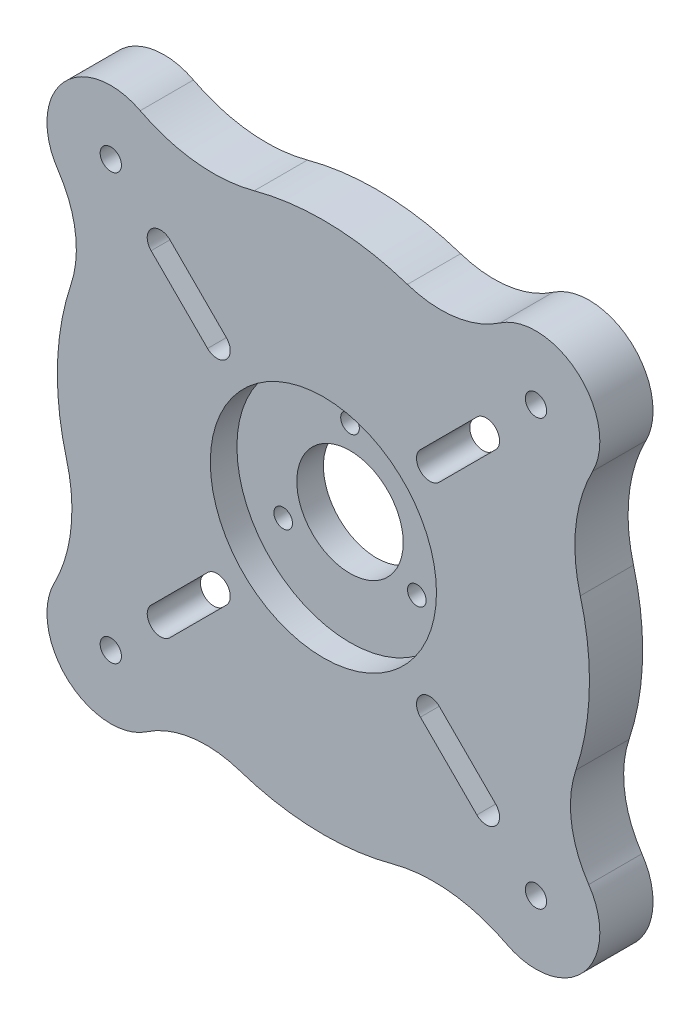
SolidWorks part; units mm, degrees
material "AISI 1020"
ref_plane "Front Plane" through (0, 0, 0) normal (0, 0, 1) x (1, 0, 0)
ref_plane "Top Plane" through (0, 0, 0) normal (0, 1, 0) x (1, 0, 0)
ref_plane "Right Plane" through (0, 0, 0) normal (1, 0, 0) x (0, 0, -1)
sketch "Sketch2" plane through (0, 0, 0) normal (0, 0, 1) x (1, 0, 0)
  line L0 (39.9515, 39.9515) -> (-39.9515, -39.9515) construction
  line L1 (48.4368, 31.4663) -> (-31.4663, -48.4368) construction
  line L2 (31.4663, 48.4368) -> (-48.4368, -31.4663) construction
  line L3 (0, 0) -> (0, 50) construction
  line L4 (-39.9515, 39.9515) -> (39.9515, -39.9515) construction
  line L5 (-48.4368, 31.4663) -> (31.4663, -48.4368) construction
  line L6 (-31.4663, 48.4368) -> (48.4368, -31.4663) construction
  line L7 (30.6066, 30.6066) -> (20, 20) construction
  line L8 (32.3744, 28.8388) -> (21.7678, 18.2322)
  line L9 (28.8388, 32.3744) -> (18.2322, 21.7678)
  line L10 (30.6066, -30.6066) -> (20, -20) construction
  line L11 (28.8388, -32.3744) -> (18.2322, -21.7678)
  line L12 (32.3744, -28.8388) -> (21.7678, -18.2322)
  line L13 (-30.6066, -30.6066) -> (-20, -20) construction
  line L14 (-32.3744, -28.8388) -> (-21.7678, -18.2322)
  line L15 (-28.8388, -32.3744) -> (-18.2322, -21.7678)
  line L16 (-30.6066, 30.6066) -> (-20, 20) construction
  line L17 (-28.8388, 32.3744) -> (-18.2322, 21.7678)
  line L18 (-32.3744, 28.8388) -> (-21.7678, 18.2322)
  circle A0 centre (0, 0) radius 50
  arc A1 (48.4368, 31.4663) -> (31.4663, 48.4368) centre (39.9515, 39.9515) ccw construction
  arc A2 (-48.4368, -31.4663) -> (-31.4663, -48.4368) centre (-39.9515, -39.9515) ccw construction
  arc A3 (-48.4368, 31.4663) -> (-31.4663, 48.4368) centre (-39.9515, 39.9515) cw construction
  arc A4 (48.4368, -31.4663) -> (31.4663, -48.4368) centre (39.9515, -39.9515) cw construction
  arc A5 (15.7949, 47.4396) -> (33.1904, 49.8655) centre (22.0443, 66.2094) ccw
  arc A6 (50.6023, 34.4233) -> (48.2813, 12.9969) centre (76.9925, 20.7257) ccw
  arc A7 (32.3744, 28.8388) -> (28.8388, 32.3744) centre (30.6066, 30.6066) ccw
  arc A8 (18.2322, 21.7678) -> (21.7678, 18.2322) centre (20, 20) ccw
  circle A9 centre (39.9515, 39.9515) radius 2
  arc A10 (50.6023, 34.4233) -> (33.1904, 49.8655) centre (39.9515, 39.9515) ccw
  arc A11 (47.4396, -15.7949) -> (49.8655, -33.1904) centre (66.2094, -22.0443) ccw
  arc A12 (34.4233, -50.6023) -> (12.9969, -48.2813) centre (20.7257, -76.9925) ccw
  circle A13 centre (39.9515, -39.9515) radius 2
  arc A14 (34.4233, -50.6023) -> (49.8655, -33.1904) centre (39.9515, -39.9515) ccw
  arc A15 (28.8388, -32.3744) -> (32.3744, -28.8388) centre (30.6066, -30.6066) ccw
  arc A16 (21.7678, -18.2322) -> (18.2322, -21.7678) centre (20, -20) ccw
  arc A17 (-15.7949, -47.4396) -> (-33.1904, -49.8655) centre (-22.0443, -66.2094) ccw
  arc A18 (-50.6023, -34.4233) -> (-48.2813, -12.9969) centre (-76.9925, -20.7257) ccw
  circle A19 centre (-39.9515, -39.9515) radius 2
  arc A20 (-50.6023, -34.4233) -> (-33.1904, -49.8655) centre (-39.9515, -39.9515) ccw
  arc A21 (-32.3744, -28.8388) -> (-28.8388, -32.3744) centre (-30.6066, -30.6066) ccw
  arc A22 (-18.2322, -21.7678) -> (-21.7678, -18.2322) centre (-20, -20) ccw
  arc A23 (-47.4396, 15.7949) -> (-49.8655, 33.1904) centre (-66.2094, 22.0443) ccw
  arc A24 (-34.4233, 50.6023) -> (-12.9969, 48.2813) centre (-20.7257, 76.9925) ccw
  circle A25 centre (-39.9515, 39.9515) radius 2
  arc A26 (-34.4233, 50.6023) -> (-49.8655, 33.1904) centre (-39.9515, 39.9515) ccw
  arc A27 (-28.8388, 32.3744) -> (-32.3744, 28.8388) centre (-30.6066, 30.6066) ccw
  arc A28 (-21.7678, 18.2322) -> (-18.2322, 21.7678) centre (-20, 20) ccw
  point P5 (0, 0)
  point P13 (0, 0)
  point P26 (25.3033, 25.3033)
  point P45 (25.3033, -25.3033)
  point P61 (-25.3033, -25.3033)
  point P77 (-25.3033, 25.3033)
  dimension "D1" = 100
  dimension "D4" = 12
  dimension "D5" = 2.5
  dimension "D8" = 4
  dimension "D2" = 113
  dimension "D3" = 45
  dimension "D6" = 15
  dimension "D7" = 20
  dimension "D9" = 4
extrude "Boss-Extrude1" add sketch "Sketch2" along normal blind 10 contours A0 A28 L18 A27 L17 A22 L15 A21 L14 A16 L12 A15 L11 A8 L9 A7 L8 | A24 A26 A23 A0 A25 | A6 A10 A5 A0 A9 | A12 A14 A11 A0 A13 | A18 A20 A17 A0 A19 region at (0, 0, 0) region at (36.7599, 34.6719, 0) region at (46.0898, -24.8501, 0) region at (-34.6719, 36.7599, 0) region at (-24.8501, -46.0898, 0)
sketch "Sketch3" plane through (0, 0, 10) normal (0, 0, 1) x (1, 0, 0)
  circle A0 centre (0, 0) radius 21.25
  circle A1 centre (0, 14.5) radius 1.75
  circle A2 centre (12.5574, -7.25) radius 1.75
  circle A3 centre (-12.5574, -7.25) radius 1.75
  circle A4 centre (0, 0) radius 10
  dimension "D1" = 42.5
  dimension "D2" = 3.5
  dimension "D7" = 20
  dimension "D3" = 14.5
  dimension "D4" = 3
  dimension "D5" = 19.817
  dimension "D6" = 44.9317
extrude "Cut-Extrude1" cut sketch "Sketch3" against normal blind 5
extrude "Cut-Extrude2" cut sketch "Sketch3<2>" against normal through all contours A1 | A3 | A2
sketch "Sketch3<2>" plane through (0, 0, 10) normal (0, 0, 1) x (1, 0, 0) same geometry as "Sketch3"
extrude "Cut-Extrude3" cut sketch "Sketch3<3>" against normal through all contours A4 region at (0, 0, 10)
sketch "Sketch3<3>" plane through (0, 0, 10) normal (0, 0, 1) x (1, 0, 0) same geometry as "Sketch3"
